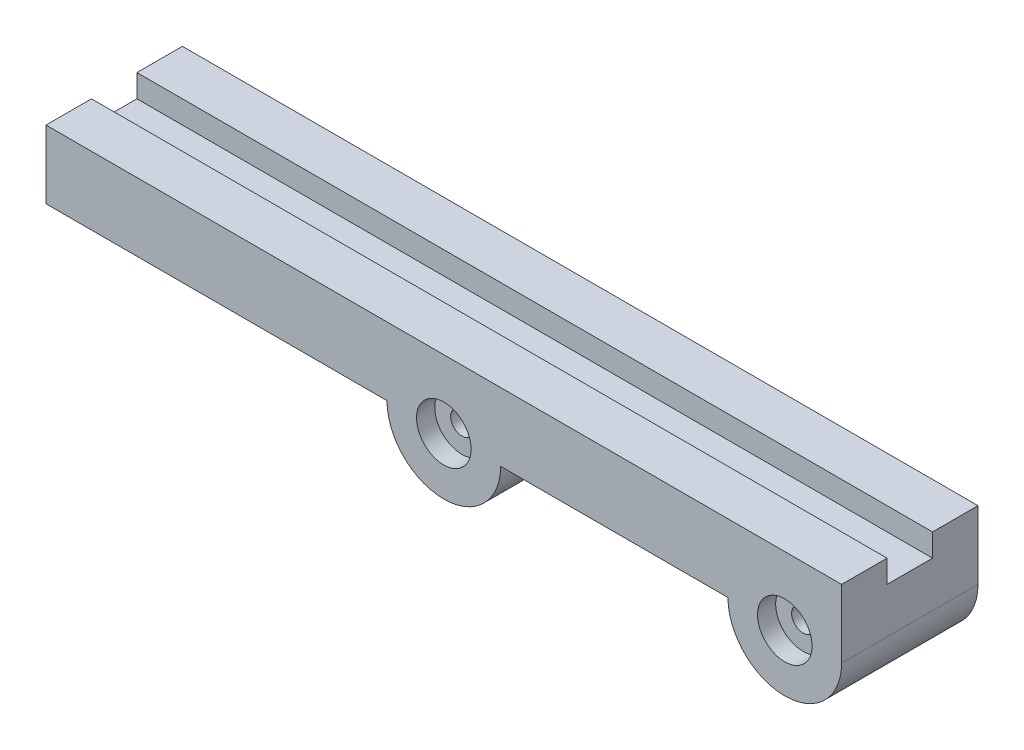
SolidWorks part; units mm, degrees
ref_plane "Front Plane" through (0, 0, 0) normal (0, 0, 1) x (1, 0, 0)
ref_plane "Top Plane" through (0, 0, 0) normal (0, 1, 0) x (1, 0, 0)
ref_plane "Right Plane" through (0, 0, 0) normal (1, 0, 0) x (0, 0, -1)
sketch "Sketch1" plane through (0, 0, 0) normal (0, 0, 1) x (1, 0, 0)
  line L0 (75, 0) -> (100, 0)
  line L1 (0, 0) -> (175, 0)
  line L2 (0, 0) -> (0, 15)
  line L3 (0, 15) -> (175, 15)
  line L4 (175, 0) -> (175, 15)
  line L5 (87.5, 0) -> (162.5, 0)
  circle A0 centre (87.5, 0) radius 12.5
  circle A1 centre (162.5, 0) radius 12.5
  point P8 (87.5, 0)
  dimension "D4" = 75
  dimension "D5" = 25
  dimension "D1" = 15
  dimension "D2" = 175
  dimension "D3" = 25
extrude "Boss-Extrude1" add sketch "Sketch1" along normal blind 30 contours A1 L4 L3 L2 L1 A0 | L1 A1 L5 | L5 A1 L1 | L0 A0 L1 | L1 A0 L0 region at (87.5, 5.3052, 0) region at (37.5, 1.7564, 0) region at (87.5, -5.3052, 0) region at (162.5, 5.3052, 0) region at (162.5, -5.3052, 0)
sketch "Sketch2" plane through (0, 0, 30) normal (0, 0, 1) x (1, 0, 0)
  line L5 (100, 0) -> (150, 0)
  line L6 (175, 0) -> (175, 15)
  line L7 (175, 15) -> (0, 15)
  line L8 (0, 15) -> (0, 0)
  line L9 (0, 0) -> (75, 0)
  line L10 (100, 0) -> (150, 0) construction
  line L11 (175, 0) -> (175, 15) construction
  line L12 (175, 15) -> (0, 15) construction
  line L13 (0, 15) -> (0, 0) construction
  line L14 (0, 0) -> (75, 0) construction
  circle A0 centre (87.5, 0) radius 2.5
  circle A1 centre (162.5, 0) radius 2.5
  arc A2 (150, 0) -> (175, 0) centre (162.5, 0) ccw
  arc A3 (75, 0) -> (100, 0) centre (87.5, 0) ccw
  arc A4 (150, 0) -> (175, 0) centre (162.5, 0) ccw construction
  arc A5 (75, 0) -> (100, 0) centre (87.5, 0) ccw construction
  circle A6 centre (87.5, 0) radius 6
  circle A7 centre (87.5, 0) radius 7.5
  circle A8 centre (162.5, 0) radius 6
  circle A9 centre (162.5, 0) radius 7.5
  dimension "D2" = 5
  dimension "D3" = 5
  dimension "D4" = 12
  dimension "D5" = 15
  dimension "D6" = 12
  dimension "D7" = 15
  dimension "D1" = 0
extrude "Cut-Extrude2" cut sketch "Sketch2" against normal up to next contours A0 | A1 region at (87.5, 0, 30) region at (162.5, 0, 30)
extrude "Cut-Extrude3" cut sketch "Sketch2<3>" against normal blind 4 contours A6 A0 | A8 A1 region at (81.6697, 0, 30) region at (156.6697, 0, 30)
sketch "Sketch2<3>" plane through (0, 0, 30) normal (0, 0, 1) x (1, 0, 0) same geometry as "Sketch2"
ref_plane "Plane1" through (0, 0, 15) normal (0, 0, 1) x (1, 0, 0)
sketch "Sketch3" plane through (0, 15, 0) normal (0, 1, 0) x (1, 0, 0)
  line L0 (0, -15) -> (175, -15) construction
  line L1 (0, -30) -> (0, 0) construction
  line L2 (175, -30) -> (175, 0) construction
  line L4 (0, -20) -> (175, -20)
  line L5 (0, -20) -> (0, -10)
  line L6 (0, -10) -> (175, -10)
  line L7 (175, -20) -> (175, -10)
  line L8 (0, -20) -> (175, -10) construction
  line L9 (0, -10) -> (175, -20) construction
  point P6 (87.5, -15)
  dimension "D1" = 10
extrude "Cut-Extrude4" cut sketch "Sketch3" against normal blind 5
